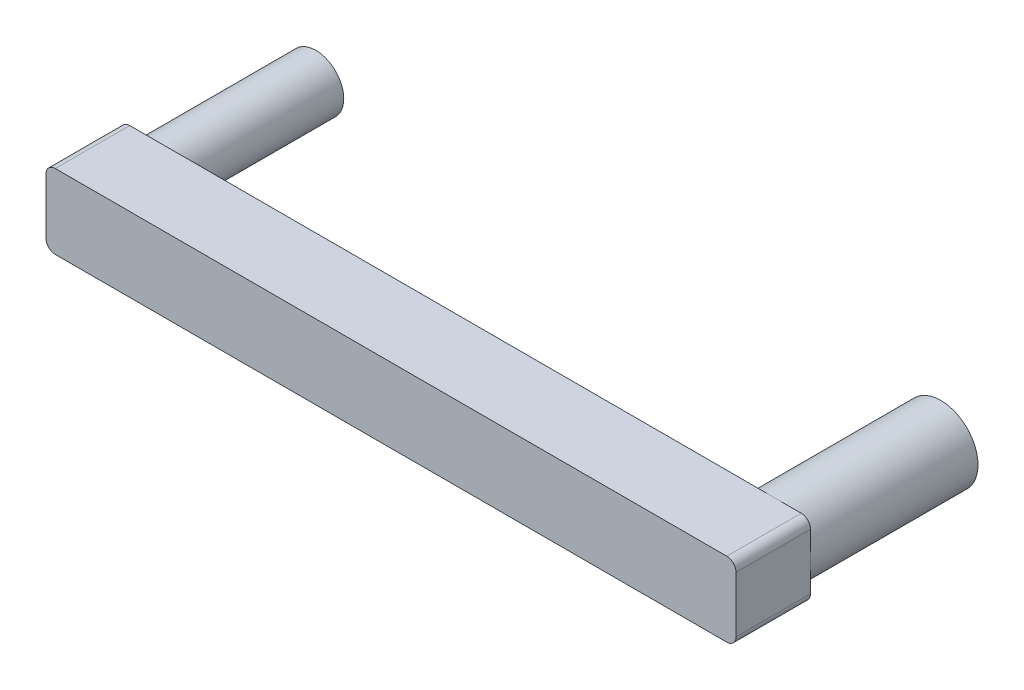
SolidWorks part; units mm, degrees
material "PLA 100% Infill"
ref_plane "Front Plane" through (0, 0, 0) normal (0, 0, 1) x (1, 0, 0)
ref_plane "Top Plane" through (0, 0, 0) normal (0, 1, 0) x (1, 0, 0)
ref_plane "Right Plane" through (0, 0, 0) normal (1, 0, 0) x (0, 0, -1)
sketch "Sketch1" plane through (0, 0, 0) normal (0, 0, 1) x (1, 0, 0)
  line L0 (0, -2) -> (37.08, -2) construction
  line L1 (0, 0) -> (37.08, 0)
  line L2 (0, 0) -> (0, -4)
  line L3 (0, -4) -> (37.08, -4)
  line L4 (37.08, 0) -> (37.08, -4)
  line L5 (36.2347, -2.6667) -> (33.9253, -2.6667)
  line L6 (33.9253, -2.6667) -> (35.08, -0.6667)
  line L7 (35.08, -0.6667) -> (36.2347, -2.6667)
  line L8 (35.08, -0.6667) -> (35.08, -2.6667) construction
  line L10 (35.6574, -1.6667) -> (33.9253, -2.6667) construction
  circle A0 centre (1.5, -2) radius 1.5
  circle A1 centre (35.08, -2) radius 2
  point P18 (35.08, -2)
  dimension "D2" = 3
  dimension "D3" = 4
  dimension "D5" = 2
  dimension "D1" = 4
  dimension "D4" = 33.58
extrude "Boss-Extrude1" add sketch "Sketch1" along normal blind 4 contours L1 L4 L3 L2
extrude "Boss-Extrude2" add sketch "Sketch1<3>" against normal blind 9 contours L0 A1 | A1 L0 | A0 L0 | L0 A0 | L5 L6 L7 region at (1.5, -2, 0) region at (36.4542, -0.6258, 0)
sketch "Sketch1<3>" plane through (0, 0, 0) normal (0, 0, 1) x (1, 0, 0) same geometry as "Sketch1"
ref_plane "Plane1" [suppressed] through (0, 0, -19) normal (0, 0, -1) x (-1, 0, 0)
fillet "Fillet1" radius 0.5 4 edges at (0, -4, 2) (0, 0, 2) (37.08, 0, 2) (37.08, -4, 2)
